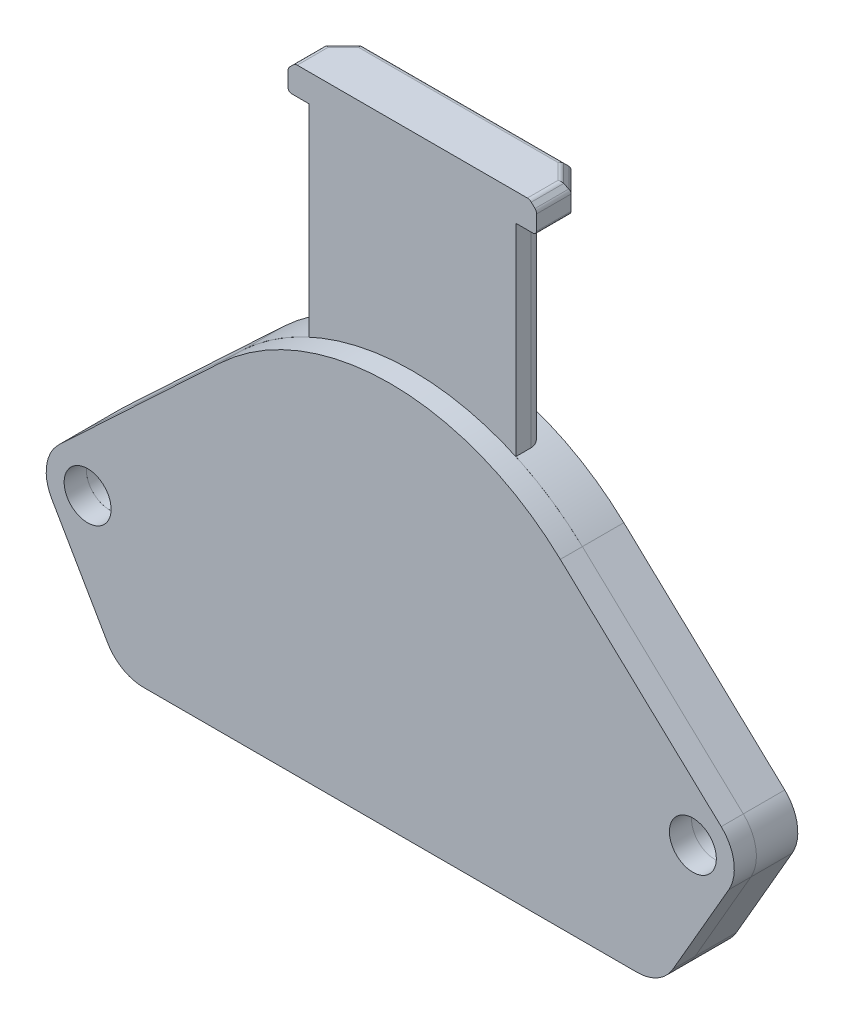
SolidWorks part; units mm, degrees
ref_plane "Front Plane" through (0, 0, 0) normal (0, 0, 1) x (1, 0, 0)
ref_plane "Top Plane" through (0, 0, 0) normal (0, 1, 0) x (1, 0, 0)
ref_plane "Right Plane" through (0, 0, 0) normal (1, 0, 0) x (0, 0, -1)
sketch "Sketch1" plane through (0, 0, 0) normal (0, 0, 1) x (1, 0, 0)
  line L0 (-12.3175, 13.1255) -> (-23.9729, 2.1876)
  line L1 (12.3175, 13.1255) -> (23.9729, 2.1876)
  line L2 (-21.92, 0) -> (21.92, 0) construction
  line L3 (-24.5181, -1.5) -> (-19.6106, -10)
  line L4 (-19.6106, -10) -> (19.6106, -10)
  line L5 (0, -10) -> (0, 0) construction
  line L6 (24.5181, -1.5) -> (19.6106, -10)
  arc A1 (-23.9729, 2.1876) -> (-24.5181, -1.5) centre (-21.92, 0) ccw
  arc A2 (24.5181, -1.5) -> (23.9729, 2.1876) centre (21.92, 0) ccw
  circle A3 centre (-21.92, 0) radius 1.7
  circle A4 centre (21.92, 0) radius 1.7
  arc A5 (12.3175, 13.1255) -> (-12.3175, 13.1255) centre (0, 0) ccw
  dimension "D1" = 43.84
  dimension "D2" = 18
  dimension "D3" = 6
  dimension "D5" = 3.4
  dimension "D4" = 10
  dimension "D6" = 60
extrude "Boss-Extrude1" add sketch "Sketch1" along normal blind 1.6
fillet "Fillet3" radius 3 2 edges at (19.6106, -10, 0.8) (-19.6106, -10, 0.8)
sketch "Sketch2" plane through (0, 0, 0) normal (0, 0, -1) x (-1, 0, 0)
  line L0 (-8.7583, 3) -> (8.7583, 3) construction
  line L1 (-7.3506, 1.5) -> (7.3506, 1.5)
  line L2 (-10.1659, 4.5) -> (10.1659, 4.5)
  line L3 (-8.7583, 1.5) -> (8.7583, 1.5) construction
  line L4 (-8.7583, 4.5) -> (8.7583, 4.5) construction
  line L5 (-6.5, 0.5936) -> (-6.5, -8) construction
  line L7 (-17.72, 0) -> (-17.72, -8)
  line L8 (17.72, 0) -> (17.72, -8)
  line L9 (-15.2027, 7.6752) -> (-8, 0) construction
  line L10 (-8, 0) -> (-8, -8) construction
  line L11 (-16.2965, 6.6487) -> (-9.5, -0.5936)
  line L12 (-9.5, -0.5936) -> (-9.5, -8)
  line L13 (-14.1089, 8.7016) -> (-6.5, 0.5936)
  line L15 (-17.8785, -8) -> (17.8785, -8)
  line L17 (18.7446, -7.5) -> (22.786, -0.5)
  line L18 (22.6043, 0.7292) -> (10.9489, 11.6671)
  line L19 (-10.9489, 11.6671) -> (-22.6043, 0.7292)
  line L20 (-22.786, -0.5) -> (-18.7446, -7.5)
  line L22 (-17.8785, -8) -> (17.8785, -8)
  line L24 (18.7446, -7.5) -> (22.786, -0.5)
  line L25 (22.6043, 0.7292) -> (10.9489, 11.6671)
  line L26 (-10.9489, 11.6671) -> (-22.6043, 0.7292)
  line L29 (-17.8785, -10) -> (17.8785, -10)
  line L31 (20.4766, -8.5) -> (24.5181, -1.5)
  line L32 (23.9729, 2.1876) -> (12.3175, 13.1255)
  line L33 (-12.3175, 13.1255) -> (-23.9729, 2.1876)
  line L34 (-24.5181, -1.5) -> (-20.4766, -8.5)
  line L36 (-17.8785, -10) -> (17.8785, -10)
  line L38 (20.4766, -8.5) -> (24.5181, -1.5)
  line L39 (23.9729, 2.1876) -> (12.3175, 13.1255)
  line L40 (-12.3175, 13.1255) -> (-23.9729, 2.1876)
  line L42 (-6.5, 1.5) -> (-6.5, -8)
  line L43 (0, 0) -> (0, -8) construction
  line L44 (6.5, 1.5) -> (6.5, -8)
  line L45 (8, 0) -> (8, -8) construction
  line L46 (9.5, -0.5936) -> (9.5, -8)
  line L47 (16.2965, 6.6487) -> (9.5, -0.5936)
  line L48 (15.2027, 7.6752) -> (8, 0) construction
  line L49 (14.1089, 8.7016) -> (6.5, 0.5936)
  line L51 (-22.786, -0.5) -> (-18.7446, -7.5)
  line L53 (-24.5181, -1.5) -> (-20.4766, -8.5)
  arc A14 (22.786, -0.5) -> (22.6043, 0.7292) centre (21.92, 0) ccw
  arc A15 (10.9489, 11.6671) -> (-10.9489, 11.6671) centre (0, 0) ccw
  arc A16 (-22.6043, 0.7292) -> (-22.786, -0.5) centre (-21.92, 0) ccw
  arc A17 (22.786, -0.5) -> (22.6043, 0.7292) centre (21.92, 0) ccw
  arc A18 (10.9489, 11.6671) -> (-10.9489, 11.6671) centre (0, 0) ccw
  circle A20 centre (-21.92, 0) radius 4.2
  circle A21 centre (-21.92, 0) radius 4.2
  circle A23 centre (21.92, 0) radius 4.2
  circle A24 centre (21.92, 0) radius 4.2
  arc A27 (-22.6043, 0.7292) -> (-22.786, -0.5) centre (-21.92, 0) ccw
  arc A31 (-18.7446, -7.5) -> (-17.8785, -8) centre (-17.8785, -7) ccw
  arc A33 (-18.7446, -7.5) -> (-17.8785, -8) centre (-17.8785, -7) ccw
  arc A34 (24.5181, -1.5) -> (23.9729, 2.1876) centre (21.92, 0) ccw
  arc A35 (12.3175, 13.1255) -> (-12.3175, 13.1255) centre (0, 0) ccw
  arc A36 (-23.9729, 2.1876) -> (-24.5181, -1.5) centre (-21.92, 0) ccw
  arc A41 (24.5181, -1.5) -> (23.9729, 2.1876) centre (21.92, 0) ccw
  arc A42 (12.3175, 13.1255) -> (-12.3175, 13.1255) centre (0, 0) ccw
  arc A43 (-23.9729, 2.1876) -> (-24.5181, -1.5) centre (-21.92, 0) ccw
  arc A45 (17.8785, -8) -> (18.7446, -7.5) centre (17.8785, -7) ccw
  arc A49 (17.8785, -8) -> (18.7446, -7.5) centre (17.8785, -7) ccw
  arc A53 (-20.4766, -8.5) -> (-17.8785, -10) centre (-17.8785, -7) ccw
  arc A55 (-20.4766, -8.5) -> (-17.8785, -10) centre (-17.8785, -7) ccw
  arc A56 (17.8785, -10) -> (20.4766, -8.5) centre (17.8785, -7) ccw
  arc A57 (17.8785, -10) -> (20.4766, -8.5) centre (17.8785, -7) ccw
  line M29 (-17.8785, -10) -> (17.8785, -10)
  line M33 (20.4766, -8.5) -> (24.5181, -1.5)
  arc M34 (24.5181, -1.5) -> (23.9729, 2.1876) centre (21.92, 0) ccw
  line M35 (23.9729, 2.1876) -> (12.3175, 13.1255)
  arc M36 (12.3175, 13.1255) -> (-12.3175, 13.1255) centre (0, 0) ccw
  line M37 (-12.3175, 13.1255) -> (-23.9729, 2.1876)
  arc M38 (-23.9729, 2.1876) -> (-24.5181, -1.5) centre (-21.92, 0) ccw
  line M39 (-24.5181, -1.5) -> (-20.4766, -8.5)
  circle M41 centre (21.92, 0) radius 1.7
  circle M42 centre (-21.92, 0) radius 1.7
  dimension "D5" = 1.5
  dimension "D7" = 8
  dimension "D8" = 1.5
  dimension "D10" = 13
  dimension "D1" = 2
  dimension "D2" = 2.5
  dimension "D3" = 2.5
  dimension "D4" = 0
  dimension "D6" = 1.5
  dimension "D9" = 1.5
extrude "Boss-Extrude2" add sketch "Sketch2" along normal blind 3 separate body contours A24 L39 A21 L26 A18 L25 M36 M37 | L26 A21 L40 L51 M38 M39 M42 | A24 L22 A21 L53 M29 M33 | A21 L26 L51 M42 | L25 A24 L24 M41 | A24 L25 L24 L38 M35 M41 M34 | A21 L22 L7 | A24 L8 L22 | L25 L49 L44 L22 L46 L47 | L42 L13 L26 L11 L12 L22 | L49 L2 L13 L1 | L42 L1 L13 | L49 L1 L44 region at (0, 3.0804, 0) region at (10.0163, 0.4649, 0) region at (6.7835, 1.1979, 0) region at (-6.7835, 1.1979, 0) region at (-10.0163, 0.4649, 0) region at (15.5175, 8.0106, 0) region at (0, -8.4508, 0) region at (19.595, -0.3437, 0) region at (20.6837, 2.6677, 0) region at (18.7009, -4.8445, 0) region at (-20.7115, 3.9186, 0) region at (-19.595, -0.3437, 0) region at (-18.7009, -4.8445, 0)
sketch "Sketch3" plane through (0, 0, 0) normal (0, 0, 1) x (1, 0, 0)
  line L0 (0, 0) -> (0, 18) construction
  circle A0 centre (-6.85, 13.3) radius 2
  arc A1 (12.3175, 13.1255) -> (-12.3175, 13.1255) centre (0, 0) ccw construction
  circle A2 centre (6.85, 13.3) radius 2
  dimension "D1" = 13.3
  dimension "D3" = 4
  dimension "D2" = 13.7
extrude "Cut-Extrude1" cut sketch "Sketch3" against normal through all draft 20
chamfer "Chamfer1" distance 2 angle 30 3 edges at (13.61, -8, 0) (0, -8, 0) (-13.61, -8, 0) first distance on face at (13.61, -8, -1.5) first distance on face at (0, -8, -1.5) first distance on face at (-13.61, -8, -1.5)
other "Move Face2" face at (-17.9631, 5.0847, -1.5) offset 4 parameters "D1"=4
other "Move Face3" face at (17.9631, 5.0847, -1.5) offset 4 parameters "D1"=4
fillet "Fillet2" radius 1.5 24 edges at (-6.5, -8, -2.5) (-14.1089, 8.7016, -1.5) (14.1089, 8.7016, -1.5) (6.5, -8, -2.5) (-13.5593, 3.7319, -1.5) (-9.5, -0.5936, -1.5) (-9.5, -8, -2.5) (-17.72, -8, -2.5) (17.72, -8, -2.5) (9.5, -8, -2.5) (9.5, -0.5936, -1.5) (13.5593, 3.7319, -1.5) (-10.1659, 4.5, -1.5) (10.1659, 4.5, -1.5) (-6.5, 1.5, -1.5) (6.5, 1.5, -1.5) (17.72, -8.5774, -1) (9.5, -8.5774, -1) (6.5, -8.5774, -1) (-6.5, -8.5774, -1) (-9.5, -8.5774, -1) (-17.72, -8.5774, -1) (17.72, -0.1727, -1.5) (-17.72, -0.1727, -1.5)
sketch "Sketch4" plane through (0, 0, 0) normal (0, 0, 1) x (1, 0, 0)
  line L0 (0, 18) -> (0, 33) construction
  line L1 (-9, 33) -> (9, 33)
  line L2 (9, 33) -> (9, 31)
  line L3 (9, 31) -> (7.5, 31)
  line L4 (7.5, 31) -> (7.5, 16.3631)
  line L5 (-7.5, 31) -> (7.5, 31)
  line L7 (-7.5, 31) -> (-7.5, 16.3631)
  line L8 (-9, 31) -> (-7.5, 31)
  line L9 (-9, 33) -> (-9, 31)
  arc A0 (12.3175, 13.1255) -> (-12.3175, 13.1255) centre (0, 0) ccw construction
  arc A2 (7.5, 16.3631) -> (-7.5, 16.3631) centre (0, 0) ccw
  point P7 (-7.5, 16.3631)
  dimension "D2" = 15
  dimension "D3" = 1.5
  dimension "D4" = 15
  dimension "D6" = 2
extrude "Boss-Extrude3" add sketch "Sketch4" against normal up to surface (3 mm away) contours L0 L5 L3 L2 L1 | L5 L0 L1 L9 L8 | L0 L5 L7 | L0 L4 L5 region at (-3.8248, 24.2237, 0) region at (3.8248, 24.2237, 0) region at (-4.5, 32, 0) region at (4.5, 32, 0) up to face at (13.6, -2.5649, -3)
extrude "Boss-Extrude4" add sketch "Sketch4<3>" against normal blind 1 from surface contours L5 L0 L1 L9 L8 | L0 L5 L3 L2 L1 region at (-4.5, 32, 0) region at (4.5, 32, 0) starting at face at (13.6, -2.5649, -3)
sketch "Sketch4<3>" plane through (0, 0, 0) normal (0, 0, 1) x (1, 0, 0) same geometry as "Sketch4"
chamfer "Chamfer6" distance 1.5 angle 45 2 edges at (-9, 32, -4) (9, 32, -4)
chamfer "Chamfer3" distance 0.5 angle 45 5 edges at (9, 33, -1.25) (0, 33, -4) (-9, 33, -1.25) (8.25, 33, -3.25) (-8.25, 33, -3.25)
fillet "Fillet6" radius 0.4 10 edges at (-8.5, 33, -1.1464) (0, 33, -3.5) (0, 32.5, -4) (-9, 32.5, -1.25) (9, 32.5, -1.25) (8.5, 33, -1.1464) (8.25, 32.5, -3.25) (7.8964, 33, -2.8964) (-7.8964, 33, -2.8964) (-8.25, 32.5, -3.25)
chamfer "Chamfer5" distance 1.5 angle 45 2 edges at (7.5, 23.6815, -3) (-7.5, 23.6815, -3)
fillet "Fillet7" radius 1 4 edges at (6, 23.9853, -3) (-6, 23.9853, -3) (7.5, 23.6815, -1.5) (-7.5, 23.6815, -1.5)
fillet "Fillet8" radius 0.25 5 edges at (9, 31, -1.25) (8.25, 31, -3.25) (0, 31, -4) (-8.25, 31, -3.25) (-9, 31, -1.25)
